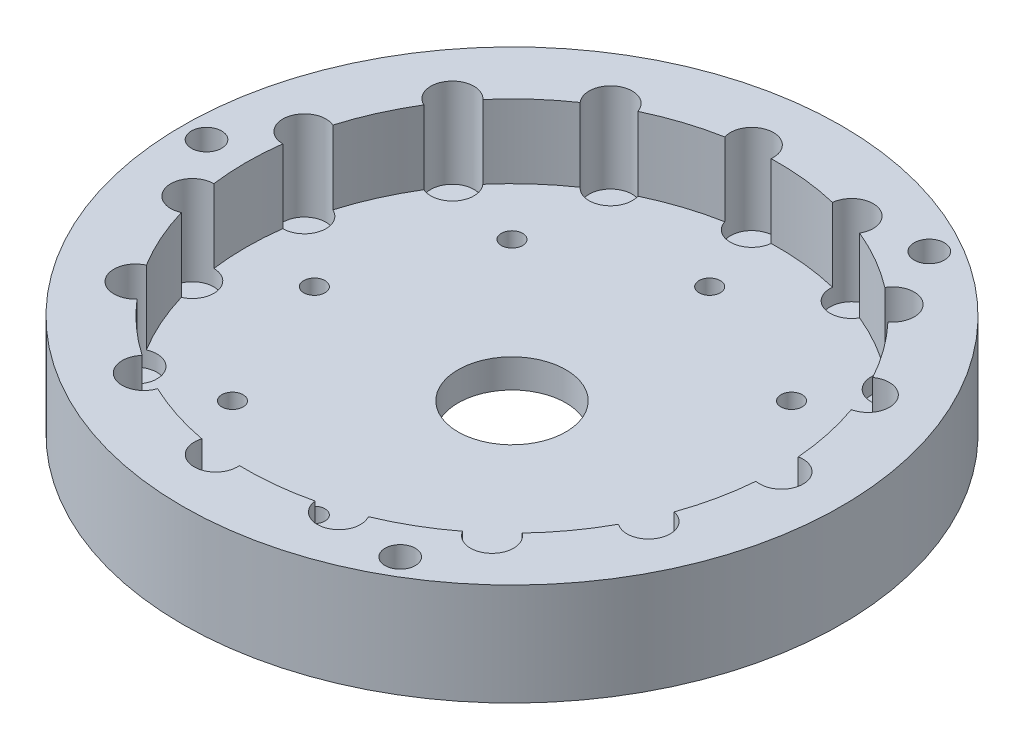
SolidWorks part; units mm, degrees
ref_plane "Front Plane" through (0, 0, 0) normal (0, 0, 1) x (1, 0, 0)
ref_plane "Top Plane" through (0, 0, 0) normal (0, 1, 0) x (1, 0, 0)
ref_plane "Right Plane" through (0, 0, 0) normal (1, 0, 0) x (0, 0, -1)
sketch "Sketch1" plane through (0, 0, 0) normal (0, 1, 0) x (1, 0, 0)
  line L0 (0, 0) -> (-42.5, 0) construction
  circle A0 centre (0, 0) radius 7.5
  circle A1 centre (0, 0) radius 45.85
  circle A2 centre (0, 0) radius 37.5 construction
  circle A3 centre (37.5, 0) radius 3
  circle A4 centre (34.258, 15.2526) radius 3
  circle A5 centre (25.0924, 27.8679) radius 3
  circle A6 centre (11.5881, 35.6646) radius 3
  circle A7 centre (-3.9198, 37.2946) radius 3
  circle A8 centre (-18.75, 32.476) radius 3
  circle A9 centre (-30.3381, 22.0419) radius 3
  circle A10 centre (-36.6805, 7.7967) radius 3
  circle A11 centre (-36.6805, -7.7967) radius 3
  circle A12 centre (-30.3381, -22.0419) radius 3
  circle A13 centre (-18.75, -32.476) radius 3
  circle A14 centre (-3.9198, -37.2946) radius 3
  circle A15 centre (11.5881, -35.6646) radius 3
  circle A16 centre (25.0924, -27.8679) radius 3
  circle A17 centre (34.258, -15.2526) radius 3
  circle A19 centre (0, 0) radius 27.5 construction
  circle A20 centre (27.5, 0) radius 1.48
  circle A21 centre (19.4454, -19.4454) radius 1.48
  circle A22 centre (0, -27.5) radius 1.48
  circle A23 centre (-19.4454, -19.4454) radius 1.48
  circle A24 centre (-27.5, 0) radius 1.48
  circle A25 centre (-19.4454, 19.4454) radius 1.48
  circle A26 centre (0, 27.5) radius 1.48
  circle A27 centre (19.4454, 19.4454) radius 1.48
  arc A28 (36.8833, 2.9359) -> (34.8888, 12.3197) centre (0, 0) ccw
  arc A29 (34.8888, -12.3197) -> (36.8833, -2.9359) centre (0, 0) ccw
  arc A30 (26.8616, -25.4451) -> (32.5004, -17.6839) centre (0, 0) ccw
  arc A31 (14.1898, -34.1709) -> (22.4979, -29.3742) centre (0, 0) ccw
  arc A32 (-0.9355, -36.9882) -> (8.6053, -35.9854) centre (0, 0) ccw
  arc A33 (-15.8991, -33.4099) -> (-6.7752, -36.3744) centre (0, 0) ccw
  arc A34 (-28.1135, -24.0547) -> (-20.9843, -30.4739) centre (0, 0) ccw
  arc A35 (-35.4669, -10.5403) -> (-31.5649, -19.3043) centre (0, 0) ccw
  arc A36 (-36.6878, 4.7967) -> (-36.6878, -4.7967) centre (0, 0) ccw
  arc A37 (-31.5649, 19.3043) -> (-35.4669, 10.5403) centre (0, 0) ccw
  arc A38 (-20.9843, 30.4739) -> (-28.1135, 24.0547) centre (0, 0) ccw
  arc A39 (-6.7752, 36.3744) -> (-15.8991, 33.4099) centre (0, 0) ccw
  arc A40 (8.6053, 35.9854) -> (-0.9355, 36.9882) centre (0, 0) ccw
  arc A41 (22.4979, 29.3742) -> (14.1898, 34.1709) centre (0, 0) ccw
  arc A42 (32.5004, 17.6839) -> (26.8616, 25.4451) centre (0, 0) ccw
  circle A43 centre (-42.5, 0) radius 2.1
  circle A44 centre (21.25, 36.8061) radius 2.1
  circle A45 centre (21.25, -36.8061) radius 2.1
  point P38 (0, 0)
  point P57 (0, 0)
  point P58 (19.4454, -57.9788)
  point P87 (0, 0)
  point P88 (0, 0)
  point P92 (0, 0)
  dimension "D2" = 15
  dimension "D3" = 75
  dimension "D4" = 91.7
  dimension "D5" = 6
  dimension "D8" = 2.96
  dimension "D9" = 55
  dimension "D6" = 37
  dimension "D12" = 4.2
  dimension "D11" = 42.5
  dimension "D1" = 15
  dimension "D7" = 8
  dimension "D10" = 15
  dimension "D13" = 3
extrude "Boss-Extrude1" add sketch "Sketch1" against normal blind 4 contours A4 A42 A5 A41 A6 A40 A7 A39 A8 A38 A9 A37 A10 A36 A11 A35 A12 A34 A13 A33 A14 A32 A15 A31 A16 A30 A17 A29 A3 A28 A0 A20 A21 A22 A23 A24 A25 A26 A27 | A3 | A17 | A4 | A5 | A6 | A7 | A8 | A9 | A10 | A11 | A12 | A13 | A14 | A15 | A16 | A1 A42 A4 A28 A3 A29 A17 A30 A16 A31 A15 A32 A14 A33 A13 A34 A12 A35 A11 A36 A10 A37 A9 A38 A8 A39 A7 A40 A6 A41 A5 | A22 | A23 | A24 | A25 | A26 | A27 | A20 | A21 region at (-45.7203, 0, 0) region at (37.5, 0, 0) region at (33.4543, 0, 0) region at (34.258, 0, -15.2526) region at (34.258, 0, 15.2526) region at (25.0924, 0, -27.8679) region at (25.0924, 0, 27.8679) region at (11.5881, 0, -35.6646) region at (11.5881, 0, 35.6646) region at (-3.9198, 0, -37.2946) region at (-3.9198, 0, 37.2946) region at (-18.75, 0, -32.476) region at (-18.75, 0, 32.476) region at (-30.3381, 0, -22.0419) region at (-30.3381, 0, 22.0419) region at (-36.6805, 0, -7.7967) region at (-36.6805, 0, 7.7967) region at (27.5, 0, 0) region at (19.4454, 0, 19.4454) region at (0, 0, 27.5) region at (-19.4454, 0, 19.4454) region at (-27.5, 0, 0) region at (-19.4454, 0, -19.4454) region at (0, 0, -27.5) region at (19.4454, 0, -19.4454)
extrude "Cut-Extrude1" cut sketch "Sketch1<6>" against normal blind 2.22 contours A24 | A25 | A26 | A27 | A20 | A21 | A22 | A23 | A10 | A11 | A9 | A12 | A13 | A14 | A15 | A16 | A17 | A3 | A4 | A5 | A6 | A7 | A8 region at (37.5, 0, 0) region at (34.258, 0, -15.2526) region at (34.258, 0, 15.2526) region at (25.0924, 0, -27.8679) region at (25.0924, 0, 27.8679) region at (11.5881, 0, -35.6646) region at (11.5881, 0, 35.6646) region at (-3.9198, 0, -37.2946) region at (-3.9198, 0, 37.2946) region at (-18.75, 0, -32.476) region at (-18.75, 0, 32.476) region at (-30.3381, 0, -22.0419) region at (-30.3381, 0, 22.0419) region at (-36.6805, 0, -7.7967) region at (-36.6805, 0, 7.7967) region at (27.5, 0, 0) region at (19.4454, 0, 19.4454) region at (0, 0, 27.5) region at (-19.4454, 0, 19.4454) region at (-27.5, 0, 0) region at (-19.4454, 0, -19.4454) region at (0, 0, -27.5) region at (19.4454, 0, -19.4454)
sketch "Sketch1<6>" plane through (0, 0, 0) normal (0, 1, 0) x (1, 0, 0) same geometry as "Sketch1"
extrude "Boss-Extrude2" add sketch "Sketch1<7>" along normal blind 10.22 contours A1 A42 A4 A28 A3 A29 A17 A30 A16 A31 A15 A32 A14 A33 A13 A34 A12 A35 A11 A36 A10 A37 A9 A38 A8 A39 A7 A40 A6 A41 A5 region at (-45.7203, 0, 0)
sketch "Sketch1<7>" plane through (0, 0, 0) normal (0, 1, 0) x (1, 0, 0) same geometry as "Sketch1"
equation "\"bearing_21_OD\"= 21mm"
equation "\"D2@Sketch1\"=\"bearing_15_OD\"+\"bearing_21_outer_clearance\""
equation "\"pin_cirlce_diameter\"= 75mm"
equation "\"D3@Sketch1\"=\"pin_cirlce_diameter\""
equation "\"pin_diam\"= 6mm"
equation "\"D5@Sketch1\"=\"pin_diam\""
equation "\"gear_thickness\"= 4mm"
equation "\"ball_bearing_diam\"= 2.96mm"
equation "\"bearing_21_outer_clearance\"= 0mm'change this"
equation "\"bearing_15_OD\"= 15mm"
equation "\"bearing_15_outer_clearance\"= 0mm'change this"
equation "\"D8@Sketch1\"=\"ball_bearing_diam\""
equation "\"D1@Cut-Extrude1\"=\"ball_bearing_diam\"*0.75"
equation "\"thrust_bearing_thickness\"= 5mm'measure this irl and change"
equation "\"D1@Boss-Extrude2\"=\"ball_bearing_diam\"*0.75mm+2*\"gear_thickness\""
